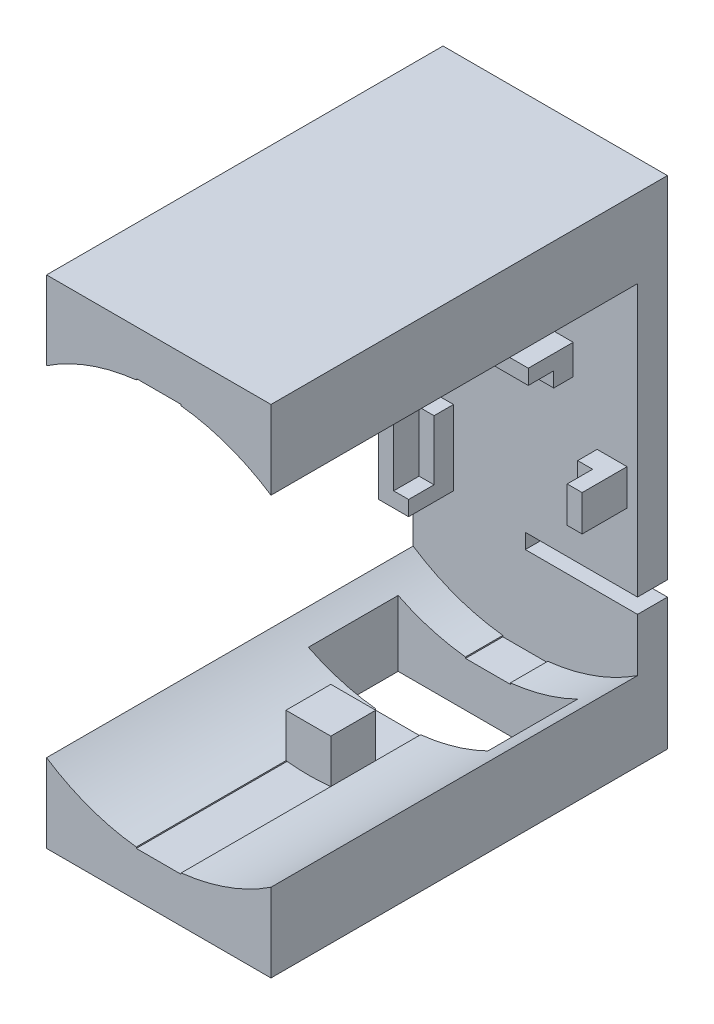
SolidWorks part; units mm, degrees
ref_plane "Front Plane" through (0, 0, 0) normal (0, 0, 1) x (1, 0, 0)
ref_plane "Top Plane" through (0, 0, 0) normal (0, 1, 0) x (1, 0, 0)
ref_plane "Right Plane" through (0, 0, 0) normal (1, 0, 0) x (0, 0, -1)
sketch "Sketch1" plane through (0, 0, 0) normal (0, 0, 1) x (1, 0, 0)
  line L0 (-5.7863, 0) -> (7.2515, 0) construction
  line L1 (-7.5, 16.6) -> (7.5, 16.6)
  line L2 (-7.5, 16.6) -> (-7.5, -16.6)
  line L3 (-7.5, -16.6) -> (7.5, -16.6)
  line L4 (7.5, 16.6) -> (7.5, -16.6)
  line L5 (0, 21.636) -> (0, -26241.9537) construction
  line L7 (-1.5, 13.6) -> (1.5, 13.6)
  line L8 (-1.5, 13.6) -> (-1.5, 10.6)
  line L9 (-1.5, 10.6) -> (1.5, 10.6)
  line L10 (1.5, 13.6) -> (1.5, 10.6)
  line L11 (-1.5, -10.6) -> (1.5, -10.6)
  line L12 (-1.5, -10.6) -> (-1.5, -13.6)
  line L13 (-1.5, -13.6) -> (1.5, -13.6)
  line L14 (1.5, -10.6) -> (1.5, -13.6)
  circle A0 centre (0, 0) radius 13.6
  point P11 (0, 16.6)
  point P12 (0, -16.6)
  point P21 (0, 13.6)
  point P22 (0, -13.6)
  point P23 (-7.5, 0)
  dimension "D1" = 27.2
  dimension "D2" = 3
  dimension "D3" = 3
  dimension "D4" = 15
extrude "Boss-Extrude1" add sketch "Sketch1" along normal blind 14.5 contours A0 L4 L1 L2 L8 L7 L10 | L10 A0 L8 L9 | L12 A0 L14 L11 | A0 L2 L3 L4 L14 L13 L12 region at (0, 14.6802, 0) region at (0, -14.6802, 0) region at (0, 12.0863, 0) region at (0, -12.0863, 0)
extrude "Boss-Extrude3" add sketch "Sketch1<3>" against normal blind 2 contours L4 A0 L10 L9 L8 L2 L12 L11 L14 | A0 L4 L1 L2 L8 L7 L10 | A0 L2 L3 L4 L14 L13 L12 | L8 L7 L10 L9 | L12 L11 L14 L13 region at (0, 14.6802, 0) region at (0, 0, 0) region at (0, -14.6802, 0)
sketch "Sketch1<3>" plane through (0, 0, 0) normal (0, 0, 1) x (1, 0, 0) same geometry as "Sketch1"
extrude "Cut-Extrude1" cut sketch "Sketch1<4>" along normal offset from surface (11.5 mm away) 3 contours L12 A0 L14 L11 | L10 A0 L8 L9 region at (0, 12.0863, 0) region at (0, -12.0863, 0) up to face at (0, -12.0793, 14.5)
sketch "Sketch1<4>" plane through (0, 0, 0) normal (0, 0, 1) x (1, 0, 0) same geometry as "Sketch1"
extrude "Boss-Extrude4" add sketch "Sketch1<5>" along normal offset from surface (24.5 mm away) 10 contours A0 L4 L1 L2 L8 L7 L10 | A0 L2 L3 L4 L14 L13 L12 region at (0, 14.6802, 0) region at (0, -14.6802, 0) up to face at (0, 13.8547, 14.5) offset beyond the face yes
sketch "Sketch1<5>" plane through (0, 0, 0) normal (0, 0, 1) x (1, 0, 0) same geometry as "Sketch1"
sketch "Sketch2" plane through (0, 0, 0) normal (0, 0, 1) x (1, 0, 0)
  line L0 (0, 0) -> (50000, 0) construction
  line L1 (-3.2, 5.8) -> (3.2, 5.8)
  line L2 (-3.2, 5.8) -> (-3.2, 4.8)
  line L3 (-3.2, 4.8) -> (3.2, 4.8)
  line L4 (3.2, 5.8) -> (3.2, 4.8)
  line L5 (-6.8, -1.8) -> (-4.8, -1.8)
  line L6 (-6.8, -1.8) -> (-6.8, -6.8)
  line L7 (-6.8, -6.8) -> (-4.8, -6.8)
  line L8 (-4.8, -1.8) -> (-4.8, -6.8)
  line L9 (-4.8, -1.8) -> (-5.8, -1.8)
  line L10 (-4.8, -1.8) -> (-4.8, -5.8)
  line L11 (-4.8, -5.8) -> (-5.8, -5.8)
  line L12 (-5.8, -1.8) -> (-5.8, -5.8)
  line L13 (6.8, 0.4) -> (4.8, 0.4)
  line L14 (6.8, 0.4) -> (6.8, -2)
  line L15 (6.8, -2) -> (4.8, -2)
  line L16 (4.8, 0.4) -> (4.8, -2)
  line L17 (6.8, 0.4) -> (5.8, 0.4)
  line L18 (6.8, 0.4) -> (6.8, -2)
  line L19 (6.8, -2) -> (5.8, -2)
  line L20 (5.8, 0.4) -> (5.8, -2)
  line L21 (-3.2, 5.8) -> (3.2, 5.8)
  line L22 (-3.2, 5.8) -> (-3.2, 3.8)
  line L23 (-3.2, 3.8) -> (3.2, 3.8)
  line L24 (3.2, 5.8) -> (3.2, 3.8)
  line L25 (0, 0) -> (0, 50000) construction
  line L26 (7.5, 11.345) -> (7.5, -11.345) construction
  line L27 (7.5, -6.8) -> (0, -6.8)
  line L28 (7.5, -6.8) -> (7.5, -7.8)
  line L29 (7.5, -7.8) -> (0, -7.8)
  line L30 (0, -6.8) -> (0, -7.8)
  point P24 (0, 3.8)
  point P25 (-5.8, -1.8)
  dimension "D1" = 4.8
  dimension "D2" = 6.4
  dimension "D3" = 1
  dimension "D4" = 1
  dimension "D5" = 0.4
  dimension "D6" = 2
  dimension "D7" = 1
  dimension "D8" = 1
  dimension "D9" = 5.8
  dimension "D10" = 5.8
  dimension "D11" = 1
  dimension "D12" = 1
  dimension "D13" = 5.8
  dimension "D14" = 1
  dimension "D15" = 4
  dimension "D17" = 1
extrude "Boss-Extrude5" add sketch "Sketch2" along normal blind 1.3 contours L5 L12 L11 L8 | L24 L3 L22 L23 | L20 L13 L16 L15 region at (0, 4.3, 0) region at (-5.3, -3.8, 0) region at (5.3, -0.8, 0)
extrude "Boss-Extrude6" add sketch "Sketch2<3>" along normal blind 3 contours L4 L1 L2 L3 | L12 L5 L6 L7 L8 L11 | L13 L20 L15 L14 region at (0, 5.3, 0) region at (-6.1333, -4.6333, 0) region at (6.3, -0.8, 0)
sketch "Sketch2<3>" plane through (0, 0, 0) normal (0, 0, 1) x (1, 0, 0) same geometry as "Sketch2"
extrude "Cut-Extrude2" cut sketch "Sketch2<4>" against normal through all contours L27 L30 L29 L28 region at (3.75, -7.3, 0)
sketch "Sketch2<4>" plane through (0, 0, 0) normal (0, 0, 1) x (1, 0, 0) same geometry as "Sketch2"
ref_plane "Plane1" through (0, -11.345, 0) normal (0, -1, 0) x (-1, 0, 0)
sketch "Sketch3" plane through (0, -11.345, 0) normal (0, -1, 0) x (-1, 0, 0)
  line L1 (6, -2.5) -> (-6, -2.5)
  line L2 (6, -2.5) -> (6, -8.5)
  line L3 (6, -8.5) -> (-6, -8.5)
  line L4 (-6, -2.5) -> (-6, -8.5)
  line L6 (1.5, -24.5) -> (-1.5, -24.5) construction
  line L7 (1.5, 0) -> (-1.5, 0) construction
  point P8 (0, -24.5)
  point P10 (0, -8.5)
  dimension "D1" = 6
  dimension "D2" = 12
  dimension "D3" = 2.5
extrude "Cut-Extrude4" cut sketch "Sketch3" along normal up to surface (5.255 mm away) up to face at (0, -16.6, 11.25)
